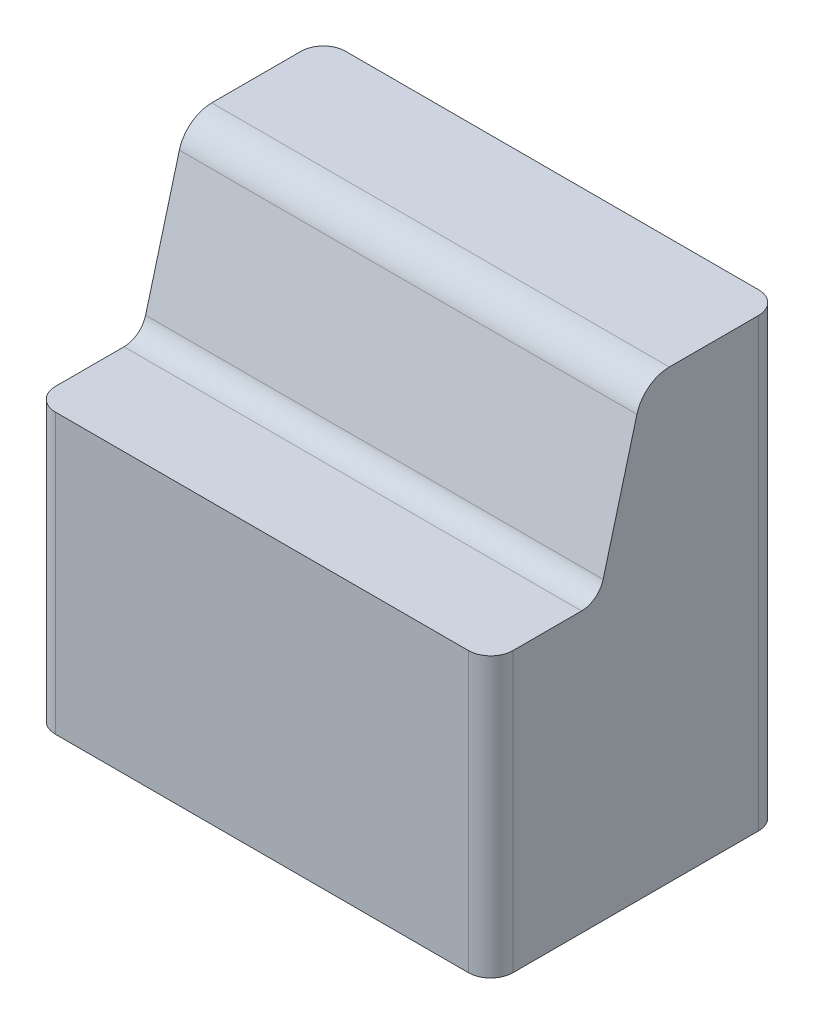
SolidWorks part; units mm, degrees
material "K110"
ref_plane "Front Plane" through (0, 0, 0) normal (0, 0, 1) x (1, 0, 0)
ref_plane "Top Plane" through (0, 0, 0) normal (0, 1, 0) x (1, 0, 0)
ref_plane "Right Plane" through (0, 0, 0) normal (1, 0, 0) x (0, 0, -1)
sketch "Sketch1" plane through (0, 0, 0) normal (1, 0, 0) x (0, 0, -1)
  line L0 (-10, 0) -> (0, 0)
  line L1 (0, 0) -> (0, -40)
  line L2 (0, -40) -> (-26, -40)
  line L3 (-26, -40) -> (-26, -15)
  line L4 (-26, -15) -> (-16.3212, -15)
  line L5 (-16.3212, -15) -> (-12.8978, -2.2235)
  arc A0 (-12.8978, -2.2235) -> (-10, 0) centre (-10, -3) cw
  dimension "D2" = 3
  dimension "D1" = 10
  dimension "D3" = 40
  dimension "D4" = 25
  dimension "D5" = 75
  dimension "D6" = 26
extrude "Boss-Extrude1" add sketch "Sketch1" along normal mid plane 41
fillet "Fillet1" radius 2 4 edges at (-20.5, -20, 0) (-20.5, -27.5, 26) (20.5, -20, 0) (20.5, -27.5, 26)
hole_wizard "M6 Tapped Hole1" positions "Sketch5" profile "Sketch3" tap size "M6" standard "ISO"
sketch "Sketch5" plane through (0, -40, 0) normal (0, -1, 0) x (-1, 0, 0)
  line L0 (-18.5, 0) -> (18.5, 0) construction
  line L1 (-20.5, -24) -> (-20.5, -2) construction
  line L2 (20.5, -24) -> (20.5, -2) construction
  point P0 (-13, -7.5)
  point P2 (13, -7.5)
  dimension "D1" = 7.5
  dimension "D2" = 7.5
  dimension "D3" = 7.5
sketch "Sketch3" plane through (13, -40, 7.5) normal (1, 0, 0) x (0, 0, -1)
  line L0 (0, 0) -> (0, 18.5022)
  line L1 (0, 18.5022) -> (2.5, 17)
  line L2 (2.5, 17) -> (2.5, 0.525)
  line L3 (2.5, 0.525) -> (3.025, 0)
  line L5 (3.025, 0) -> (0, 0)
  line L6 (-2.5, 0.525) -> (-3.025, 0) construction
  line L10 (0, 18.5022) -> (-2.5, 17) construction
  line L11 (0, -6.35) -> (0, 107.95) construction
  dimension "Tap Drill Dia." = 5
  dimension "Tap Drill Depth" = 17
  dimension "Near C'Sink Dia." = 6.05
  dimension "Near C'Sink Angle" = 90
  dimension "Drill Angle" = 118
cosmetic thread "Hole Thread1" parameters "D1"=12, "D2"=6
cosmetic thread "Hole Thread2" parameters "D1"=12, "D2"=6
fillet "Fillet2" radius 2 1 edges at (0, -15, 16.3212)
